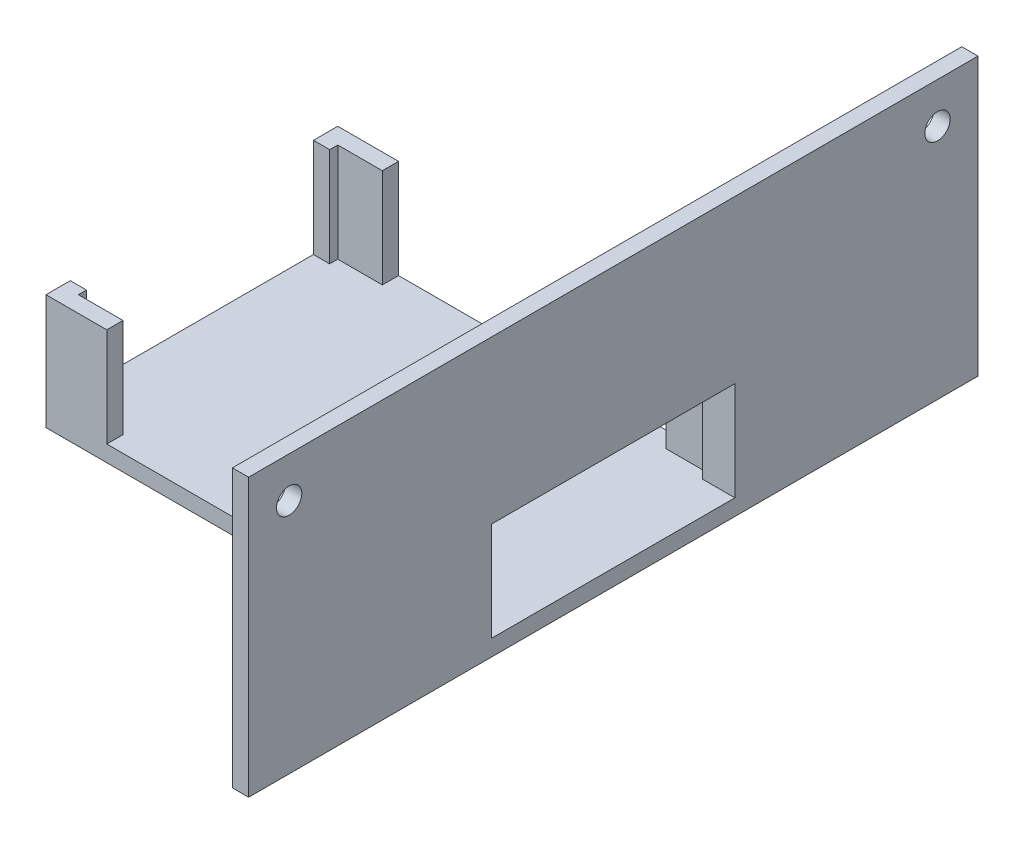
SolidWorks part; units mm, degrees
material "ABS"
ref_plane "Front Plane" through (0, 0, 0) normal (0, 0, 1) x (1, 0, 0)
ref_plane "Top Plane" through (0, 0, 0) normal (0, 1, 0) x (1, 0, 0)
ref_plane "Right Plane" through (0, 0, 0) normal (1, 0, 0) x (0, 0, -1)
sketch "Sketch1" plane through (0, 0, 0) normal (0, 1, 0) x (1, 0, 0)
  line L1 (-31.75, 45.72) -> (31.75, 45.72)
  line L2 (-31.75, 45.72) -> (-31.75, 0)
  line L3 (-31.75, 0) -> (31.75, 0)
  line L4 (31.75, 45.72) -> (31.75, 0)
  dimension "D1" = 63.5
  dimension "D2" = 45.72
extrude "Boss-Extrude1" add sketch "Sketch1" along normal blind 18.04
shell "Shell1" thickness 2.54 removed face at (0, 18.04, -22.86)
sketch "Sketch2" plane through (31.75, 0, 0) normal (1, 0, 0) x (0, 0, -1)
  line L0 (0, 0) -> (45.72, 0) construction
  line L1 (80.01, 0) -> (-34.29, 0)
  line L2 (80.01, 0) -> (80.01, 43.44)
  line L3 (80.01, 43.44) -> (-34.29, 43.44)
  line L4 (-34.29, 0) -> (-34.29, 43.44)
  line L6 (0, 18.04) -> (45.72, 18.04) construction
  point P7 (22.86, 0)
  point P8 (22.86, 0)
  dimension "D1" = 25.4
  dimension "D2" = 114.3
extrude "Boss-Extrude2" add sketch "Sketch2" along normal blind 2.54
fillet "Fillet1" radius 5.08 1 edges at (31.75, 18.04, -22.86)
sketch "Sketch3" plane through (31.75, 0, 0) normal (-1, 0, 0) x (0, 0, 1)
  line L0 (-80.01, 0) -> (-80.01, 43.44) construction
  line L1 (-80.01, 43.44) -> (34.29, 43.44) construction
  line L2 (34.29, 43.44) -> (34.29, 0) construction
  circle A0 centre (-73.66, 37.09) radius 1.9844
  circle A1 centre (27.94, 37.09) radius 1.9844
  dimension "D1" = 3.9688
  dimension "D2" = 6.35
  dimension "D3" = 6.35
  dimension "D4" = 6.35
  dimension "D5" = 6.35
extrude "Cut-Extrude1" cut sketch "Sketch3" against normal through all both and the other way through all
sketch "Sketch5" plane through (0, 0, 0) normal (0, 0, 1) x (1, 0, 0)
  line L0 (0, -23.892) -> (0, 23.892) construction
  line L1 (22.225, 2.54) -> (-22.225, 2.54)
  line L2 (22.225, 2.54) -> (22.225, 18.04)
  line L3 (22.225, 18.04) -> (-22.225, 18.04)
  line L4 (-22.225, 2.54) -> (-22.225, 18.04)
  line L5 (22.225, 2.54) -> (-22.225, 18.04) construction
  line L6 (22.225, 18.04) -> (-22.225, 2.54) construction
  line L11 (-31.75, 18.04) -> (26.67, 18.04) construction
  line L12 (-29.21, 2.54) -> (29.21, 2.54) construction
  point P0 (0, 10.29)
  dimension "D1" = 44.45
extrude "Cut-Extrude2" cut sketch "Sketch5" against normal through all
sketch "Sketch6" plane through (-31.75, 0, 0) normal (-1, 0, 0) x (0, 0, 1)
  line L0 (-45.72, 18.04) -> (0, 18.04) construction
  line L1 (-3.81, 2.54) -> (-41.91, 2.54)
  line L2 (-3.81, 2.54) -> (-3.81, 18.04)
  line L3 (-3.81, 18.04) -> (-41.91, 18.04)
  line L4 (-41.91, 2.54) -> (-41.91, 18.04)
  line L5 (-3.81, 2.54) -> (-41.91, 18.04) construction
  line L6 (-3.81, 18.04) -> (-41.91, 2.54) construction
  line L7 (-43.18, 2.54) -> (-2.54, 2.54) construction
  line L8 (-22.86, 0) -> (-22.86, 18.04) construction
  line L9 (-45.72, 0) -> (0, 0) construction
  point P0 (-22.86, 10.29)
  dimension "D1" = 38.1
extrude "Cut-Extrude3" cut sketch "Sketch6" against normal through all
fillet "Fillet2" radius 5.08 2 edges at (31.75, 11.56, -45.72) (31.75, 11.56, 0)
